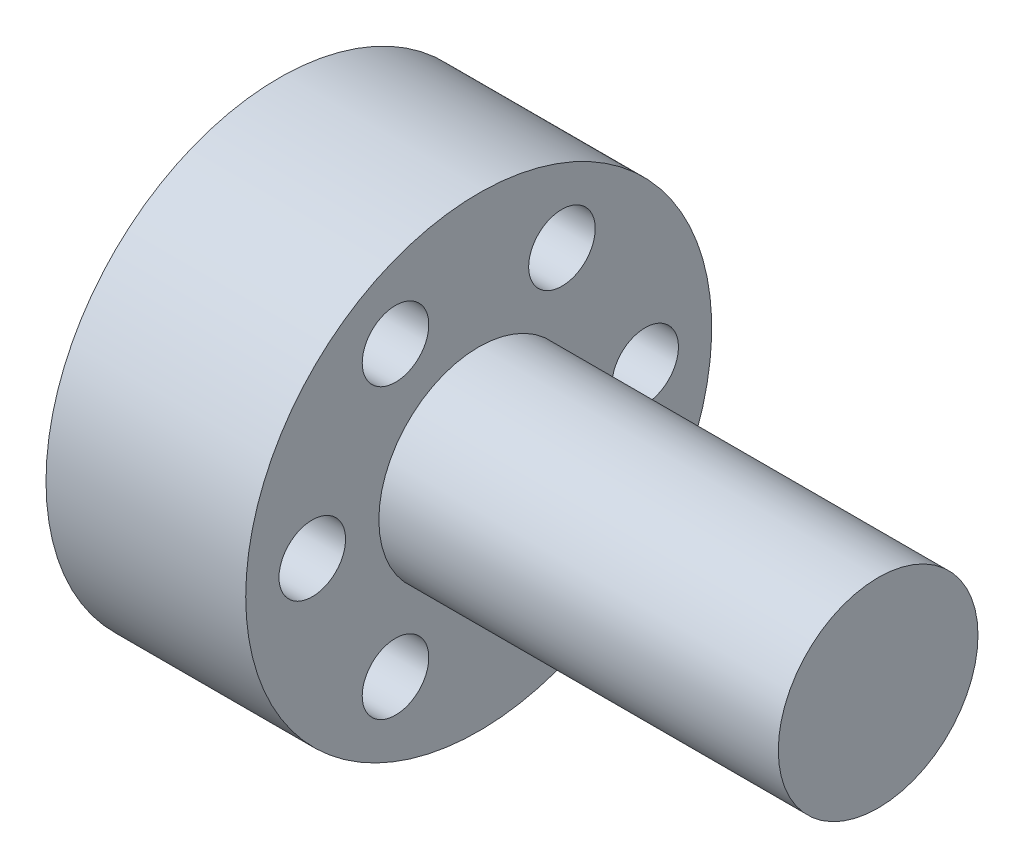
SolidWorks part; units mm, degrees
ref_plane "Спереди" through (0, 0, 0) normal (0, 0, 1) x (1, 0, 0)
ref_plane "Сверху" through (0, 0, 0) normal (0, 1, 0) x (1, 0, 0)
ref_plane "Справа" through (0, 0, 0) normal (1, 0, 0) x (0, 0, -1)
sketch "Эскиз1" plane through (0, 0, 0) normal (0, 0, 1) x (1, 0, 0)
  line L0 (0, 0) -> (100, 0)
  line L1 (0, 0) -> (0, 20)
  line L2 (0, 20) -> (10, 20)
  line L3 (10, 20) -> (10, 35)
  line L4 (10, 35) -> (40, 35)
  line L5 (40, 35) -> (40, 15)
  line L6 (40, 15) -> (100, 15)
  line L7 (100, 0) -> (100, 15)
revolve "Повернуть1" add sketch "Эскиз1" angle 360 about L0
sketch "Эскиз2" plane through (0, 0, 0) normal (1, 0, 0) x (0, 0, -1)
  circle A0 centre (0, 0) radius 4.25
extrude "Вырез-Вытянуть1" cut sketch "Эскиз2" along normal blind 20
thread "Резьба1" pitch 1.5 method cut profile "Профиль резьбы1" start angle 0, offset 0, length 20, pitch 1.5, diameter 8.5
ref_plane "Плоскость4" through (0, 0, -4.25) normal (0, -1, 0) x (0, 0, -1)
sketch "Профиль резьбы1" plane through (0, 0, -4.25) normal (0, -1, 0) x (0, 0, -1)
  line L0 (0, 0) -> (0, 1.5) construction
  line L1 (0, 0) -> (0.8119, 0.4687)
  line L2 (0.8119, 0.4687) -> (0.8119, 0.6562)
  line L3 (0.8119, 0.6562) -> (0, 1.125)
  line L4 (0.8119, 0.5625) -> (0, 0.5625) construction
  line L11 (0, 0) -> (0, 1.125)
  point P2 (0, 0)
  dimension "Pitch" = 1.5
  dimension "Profile_Angle" = 60
  dimension "Profile_Land" = 0.1875
  dimension "Profile_Height" = 0.8119
sketch "Эскиз5" plane through (0, 0, 0) normal (1, 0, 0) x (0, 0, -1)
  circle A0 centre (25, 0) radius 5
extrude "Вырез-Вытянуть2" cut sketch "Эскиз5" along normal through all
sketch "Эскиз6" plane through (0, 0, 0) normal (1, 0, 0) x (0, 0, -1)
  circle A0 centre (12.5, 21.6506) radius 5
extrude "Вырез-Вытянуть3" cut sketch "Эскиз6" along normal through all
sketch "Эскиз7" plane through (0, 0, 0) normal (1, 0, 0) x (0, 0, -1)
  circle A0 centre (-12.5, 21.6506) radius 5
extrude "Вырез-Вытянуть4" cut sketch "Эскиз7" along normal through all
sketch "Эскиз8" plane through (0, 0, 0) normal (1, 0, 0) x (0, 0, -1)
  circle A0 centre (-25, 0) radius 5
extrude "Вырез-Вытянуть5" cut sketch "Эскиз8" along normal through all
sketch "Эскиз9" plane through (0, 0, 0) normal (1, 0, 0) x (0, 0, -1)
  circle A0 centre (-12.5, -21.6506) radius 5
extrude "Вырез-Вытянуть6" cut sketch "Эскиз9" along normal through all
sketch "Эскиз10" plane through (0, 0, 0) normal (1, 0, 0) x (0, 0, -1)
  circle A0 centre (12.5, -21.6506) radius 5
extrude "Вырез-Вытянуть7" cut sketch "Эскиз10" along normal through all
